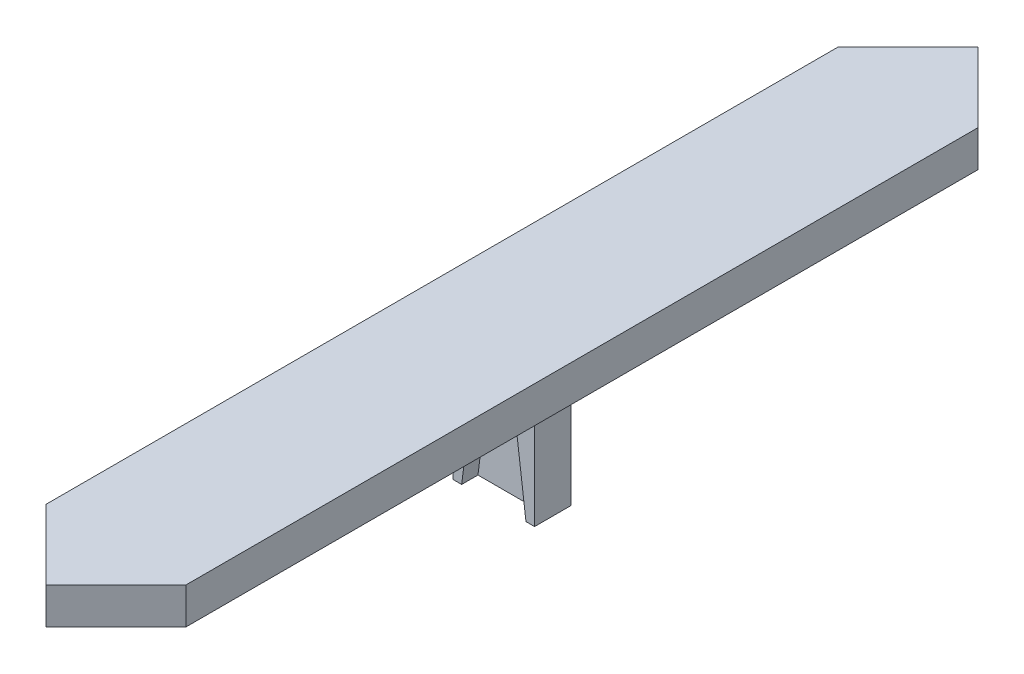
SolidWorks part; units mm, degrees
ref_plane "Front Plane" through (0, 0, 0) normal (0, 0, 1) x (1, 0, 0)
ref_plane "Top Plane" through (0, 0, 0) normal (0, 1, 0) x (1, 0, 0)
ref_plane "Right Plane" through (0, 0, 0) normal (1, 0, 0) x (0, 0, -1)
sketch "Sketch1" plane through (0, 0, 0) normal (0, 1, 0) x (1, 0, 0)
  line L0 (0, 5) -> (0, -13) construction
  line L1 (0, 0) -> (6, -6)
  line L2 (6, -6) -> (6, -74)
  line L3 (6, -74) -> (0, -80)
  line L4 (-6, -74) -> (0, -80)
  line L5 (-6, -6) -> (-6, -74)
  line L6 (0, 0) -> (-6, -6)
  point P5 (0, 0)
  point P8 (0, 0)
  point P11 (0, 0)
  point P12 (0, 0)
  dimension "D1" = 135
  dimension "D2" = 135
  dimension "D4" = 68
  dimension "D3" = 12
  dimension "D5" = 0
  dimension "D6" = 80
extrude "Boss-Extrude1" add sketch "Sketch1" along normal blind 3.125
sketch "Sketch2" plane through (0, 0, 0) normal (0, -1, 0) x (1, 0, 0)
  line L0 (0, 0) -> (0, 80) construction
  line L1 (3.5, 38.4375) -> (-3.5, 38.4375)
  line L2 (3.5, 38.4375) -> (3.5, 41.5625)
  line L3 (3.5, 41.5625) -> (-3.5, 41.5625)
  line L4 (-3.5, 38.4375) -> (-3.5, 41.5625)
  line L5 (3.5, 38.4375) -> (-3.5, 41.5625) construction
  line L6 (3.5, 41.5625) -> (-3.5, 38.4375) construction
  line L7 (6, 40) -> (-6, 40) construction
  line L8 (6, 74) -> (6, 6) construction
  line L9 (-6, 6) -> (-6, 74) construction
  point P0 (0, 40)
  dimension "D1" = 7
  dimension "D2" = 0
  dimension "D3" = 3.125
  dimension "D4" = 0
extrude "Boss-Extrude2" add sketch "Sketch2" along normal blind 10
sketch "Sketch3" plane through (0, 0, 41.5625) normal (0, 0, 1) x (1, 0, 0)
  line L0 (0, -10) -> (0, 0) construction
  line L1 (3.5, -10) -> (-3.5, -10) construction
  line L2 (3.5, 0) -> (-3.5, 0) construction
  line L3 (3.5, -15.84) -> (-3.5, -15.84)
  line L8 (3.5, -10) -> (3.5, 0) construction
  line L9 (-3.5, -10) -> (-3.5, 0) construction
  line L10 (2, -4) -> (3.5, -15.84)
  line L11 (-2, -4) -> (-3.5, -15.84)
  arc A0 (2, -4) -> (-2, -4) centre (0, -4) ccw
  point P6 (0, -5)
  dimension "D1" = 4
  dimension "D2" = 11.84
  dimension "D3" = 4
extrude "Cut-Extrude1" cut sketch "Sketch3" against normal blind 1.4
equation "\"D2@Sketch1\"=\"D1@Sketch1\""
